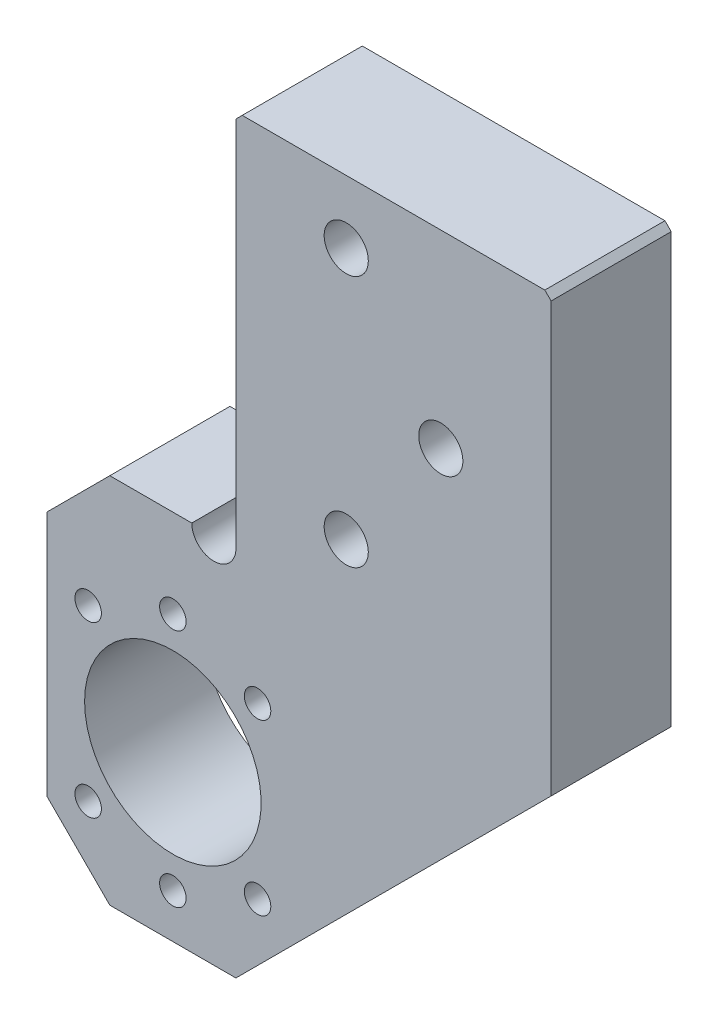
SolidWorks part; units mm, degrees
material "6061-T6 (SS)"
ref_plane "Front Plane" through (0, 0, 0) normal (0, 0, 1) x (1, 0, 0)
ref_plane "Top Plane" through (0, 0, 0) normal (0, 1, 0) x (1, 0, 0)
ref_plane "Right Plane" through (0, 0, 0) normal (1, 0, 0) x (0, 0, -1)
sketch "Sketch1" plane through (0, 0, 0) normal (0, 0, 1) x (1, 0, 0)
  line L0 (3, 33) -> (-10, 33)
  line L1 (-10, 33) -> (-20, 23)
  line L2 (-20, 23) -> (-20, -16)
  line L3 (-20, -16) -> (-10, -26)
  line L4 (-10, -26) -> (10, -26)
  line L5 (10, -26) -> (60, 24)
  line L6 (60, 24) -> (60, 93)
  line L7 (60, 93) -> (10, 93)
  line L8 (10, 93) -> (10, 33)
  line L9 (0, -10.4775) -> (0, 10.4775) construction
  line L10 (-10, -26) -> (-10, 33) construction
  line L12 (27.5, 83) -> (42.5, 83) construction
  line L13 (27.5, 83) -> (27.5, 43) construction
  line L14 (27.5, 43) -> (42.5, 43) construction
  line L15 (42.5, 83) -> (42.5, 43) construction
  line L16 (0, -19) -> (13.435, -13.435) construction
  line L17 (13.435, -13.435) -> (19, 0) construction
  line L18 (19, 0) -> (13.435, 13.435) construction
  line L19 (13.435, 13.435) -> (0, 19) construction
  line L20 (0, 19) -> (-13.435, 13.435) construction
  line L21 (-13.435, 13.435) -> (-19, 0) construction
  line L22 (-19, 0) -> (-13.435, -13.435) construction
  line L23 (-13.435, -13.435) -> (0, -19) construction
  circle A0 centre (0, 0) radius 14
  arc A1 (10, 33) -> (3, 33) centre (6.5, 33) cw
  circle A2 centre (0, 0) radius 17.5537 construction
  point P14 (0, -26)
  point P21 (42.5, 63)
  point P22 (27.5, 83)
  point P24 (27.5, 43)
  dimension "D1" = 28
  dimension "D6" = 3.5
  dimension "D2" = 20
  dimension "D3" = 26
  dimension "D4" = 33
  dimension "D5" = 20
  dimension "D7" = 10
  dimension "D8" = 17.5
  dimension "D9" = 10
  dimension "D10" = 17.5
  dimension "D11" = 15
  dimension "D12" = 10
  dimension "D13" = 40
  dimension "D14" = 38
extrude "Boss-Extrude1" add sketch "Sketch1" along normal mid plane 19.05
hole_wizard "M8x1.0 Tapped Hole1" positions "Sketch2" profile "Sketch3" tap size "M8x1.0" standard "ANSI Metric" end condition up to next
sketch "Sketch2" plane through (0, 0, 9.525) normal (0, 0, 1) x (1, 0, 0)
  line L0 (42.5, 83) -> (42.5, 43) construction
  point P0 (27.5, 43)
  point P3 (42.5, 63)
  point P7 (27.5, 83)
sketch "Sketch3" plane through (27.5, 43, 9.525) normal (1, 0, 0) x (0, -1, 0)
  line L0 (0, 0) -> (0, 19.05)
  line L1 (0, 19.05) -> (3.5, 19.05)
  line L2 (3.5, 19.05) -> (3.5, 0)
  line L5 (3.5, 0) -> (0, 0)
  line L11 (0, -6.35) -> (0, 107.95) construction
  dimension "Thru Tap Drill Dia." = 7
  dimension "Thru Tap Drill Depth" = 19.05
cosmetic thread "Hole Thread1" parameters "D2"=8
cosmetic thread "Hole Thread2" parameters "D2"=8
cosmetic thread "Hole Thread3" parameters "D2"=8
hole_wizard "M5x0.8 Tapped Hole1" positions "Sketch4" profile "Sketch5" tap size "M5x0.8" standard "ANSI Metric" end condition up to next
sketch "Sketch4" plane through (0, 0, 9.525) normal (0, 0, 1) x (1, 0, 0)
  point P0 (0, 19)
  point P3 (-13.435, 13.435)
  point P6 (13.435, 13.435)
  point P9 (13.435, -13.435)
  point P12 (0, -19)
  point P15 (-13.435, -13.435)
sketch "Sketch5" plane through (0, 19, 9.525) normal (1, 0, 0) x (0, -1, 0)
  line L0 (0, 0) -> (0, 19.05)
  line L1 (0, 19.05) -> (2.1, 19.05)
  line L2 (2.1, 19.05) -> (2.1, 0)
  line L5 (2.1, 0) -> (0, 0)
  line L11 (0, -6.35) -> (0, 107.95) construction
  dimension "Thru Tap Drill Dia." = 4.2
  dimension "Thru Tap Drill Depth" = 19.05
cosmetic thread "Hole Thread4" parameters "D2"=5
cosmetic thread "Hole Thread5" parameters "D2"=5
cosmetic thread "Hole Thread6" parameters "D2"=5
cosmetic thread "Hole Thread7" parameters "D2"=5
cosmetic thread "Hole Thread8" parameters "D2"=5
cosmetic thread "Hole Thread9" parameters "D2"=5
chamfer "Chamfer1" distance 1 2 edges at (10, 93, 0) (60, 93, 0)
